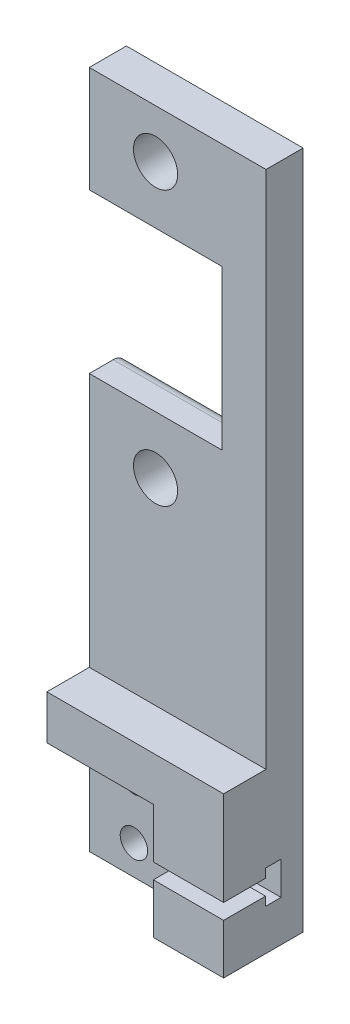
SolidWorks part; units mm, degrees
ref_plane "Front Plane" through (0, 0, 0) normal (0, 0, 1) x (1, 0, 0)
ref_plane "Top Plane" through (0, 0, 0) normal (0, 1, 0) x (1, 0, 0)
ref_plane "Right Plane" through (0, 0, 0) normal (1, 0, 0) x (0, 0, -1)
sketch "ProfileSketch3" plane through (0, 0, 0) normal (0, 0, 1) x (1, 0, 0)
  line L0 (0, 46.85) -> (15, 46.85)
  line L1 (0, 0) -> (20, 0)
  line L2 (0, 0) -> (0, 46.85)
  line L4 (20, 0) -> (20, 76.85)
  line L5 (15, 46.85) -> (15, 64.85)
  line L6 (15, 64.85) -> (0, 64.85)
  line L7 (0, 64.85) -> (0, 76.85)
  line L8 (0, 76.85) -> (20, 76.85)
  circle A0 centre (7.5, 40.35) radius 2.5
  circle A1 centre (7.5, 71.35) radius 2.5
  dimension "D8" = 5
  dimension "D6" = 20
  dimension "D1" = 46.85
  dimension "D2" = 15
  dimension "D4" = 12
  dimension "D5" = 5.5
  dimension "D7" = 6.5
  dimension "D3" = 31
  dimension "D9" = 7.5
  dimension "D10" = 18
  dimension "D11" = 6.5
extrude "ProfileBoss-Extrude1" add sketch "ProfileSketch3" along normal blind 9
sketch "MicroSwitchCutSketch4" plane through (0, 0, 9) normal (0, 0, 1) x (1, 0, 0)
  line L1 (0, 13.05) -> (12.05, 13.05)
  line L2 (0, 13.05) -> (0, 0)
  line L3 (0, 0) -> (12.05, 0)
  line L4 (12.05, 13.05) -> (12.05, 0)
  dimension "D1" = 12.05
  dimension "D2" = 13.05
extrude "MicroSwitchCut-Extrude1" cut sketch "MicroSwitchCutSketch4" against normal blind 4.8
sketch "Sketch5" plane through (0, 0, 4.2) normal (0, 0, 1) x (1, 0, 0)
  line L1 (0, 0) -> (12.05, 0) construction
  line L2 (12.05, 0) -> (12.05, 13.05) construction
  line L4 (12.05, 13.05) -> (0, 13.05) construction
  circle A0 centre (5.05, 9.7) radius 1.55
  circle A1 centre (5.05, 3.35) radius 1.55
  point P10 (11.05, 8.8)
  point P11 (0, 8.8)
  point P12 (15, 21.85)
  point P13 (11.05, 21.85)
  point P14 (15, 0)
  point P15 (15, 21.85)
  point P16 (0, 0)
  point P17 (15, 0)
  point P18 (0, 8.8)
  point P19 (0, 0)
  point P20 (-1, 8.8)
  point P21 (0, 8.8)
  point P22 (-1, 21.85)
  point P23 (-1, 8.8)
  point P24 (15, 21.85)
  point P25 (-1, 21.85)
  point P26 (15, 0)
  point P27 (15, 21.85)
  point P28 (0, 0)
  point P29 (15, 0)
  point P30 (0, 8.8)
  point P31 (0, 0)
  point P32 (11.05, 21.85)
  point P33 (-1, 21.85)
  point P34 (11.05, 8.8)
  point P35 (11.05, 21.85)
  point P36 (-1, 8.8)
  point P37 (0, 8.8)
  point P38 (0, 8.8)
  point P39 (11.05, 8.8)
  point P40 (-1, 21.85)
  point P41 (-1, 8.8)
  point P42 (11.05, 8.8)
  point P43 (11.05, 21.85)
  point P44 (0, 0)
  point P45 (15, 0)
  point P46 (0, 0)
  point P47 (0, 8.8)
  point P48 (-1, 21.85)
  point P49 (15, 21.85)
  point P50 (15, 0)
  point P51 (15, 21.85)
  point P52 (-1, 21.85)
  point P53 (-1, 8.8)
  point P54 (-1, 8.8)
  point P55 (0, 8.8)
  point P56 (-1, 21.85)
  point P57 (-1, 8.8)
  point P58 (-1, 21.85)
  point P59 (11.05, 21.85)
  point P60 (-1, 21.85)
  point P61 (-1, 8.8)
  point P62 (-1, 8.8)
  point P63 (11.05, 8.8)
  point P64 (11.05, 21.85)
  point P65 (11.05, 8.8)
  point P66 (2.75, 0)
  point P67 (-2.75, 0)
  point P68 (0, -2.75)
  point P69 (0, 2.75)
  dimension "D4" = 3.1
  dimension "D3" = 7
  dimension "D1" = 3.35
  dimension "D2" = 3.35
extrude "MicroSwitchMountingHolesCut-Extrude2" cut sketch "Sketch5" against normal blind 3.1
sketch "SmallChannelCableSketch6" plane through (0, 0, 9) normal (0, 0, 1) x (1, 0, 0)
  line L0 (12.05, 0) -> (12.05, 13.05) construction
  line L1 (12.05, 7.4) -> (20, 7.4)
  line L2 (12.05, 7.4) -> (12.05, 5.65)
  line L3 (12.05, 5.65) -> (20, 5.65)
  line L4 (20, 7.4) -> (20, 5.65)
  line L5 (20, 0) -> (20, 76.85) construction
  line L31 (12.05, 0) -> (20, 0) construction
  point P10 (1, 21.85)
  point P11 (1, 13.05)
  point P12 (16, 21.85)
  point P13 (1, 21.85)
  point P14 (16, 0)
  point P15 (16, 21.85)
  point P16 (12.05, 0)
  point P17 (16, 0)
  point P18 (1, 13.05)
  point P19 (0, 13.05)
  point P20 (1, 21.85)
  point P21 (1, 13.05)
  point P22 (16, 21.85)
  point P23 (1, 21.85)
  point P24 (16, 0)
  point P25 (16, 21.85)
  point P26 (0, 0)
  point P27 (16, 0)
  point P28 (0, 13.05)
  point P29 (0, 0)
  point P30 (12.05, 13.05)
  point P31 (1, 13.05)
  point P32 (1, 13.05)
  point P33 (0, 13.05)
  point P34 (12.05, 0)
  point P35 (12.05, 13.05)
  point P36 (0, 0)
  point P37 (12.05, 0)
  point P38 (0, 13.05)
  point P39 (0, 0)
  point P40 (12.05, 13.05)
  point P41 (1, 13.05)
  point P42 (12.05, 0)
  point P43 (12.05, 13.05)
  point P44 (5.05, 9.7)
  point P45 (6.5323, 10.1532)
  point P46 (5.05, 3.35)
  point P47 (6.5323, 3.8032)
  point P48 (5.05, 9.7)
  point P49 (6.5323, 10.1532)
  point P50 (5.05, 3.35)
  point P51 (6.5323, 3.8032)
  point P52 (0, 0)
  point P53 (16, 0)
  point P54 (0, 0)
  point P55 (0, 13.05)
  point P56 (1, 21.85)
  point P57 (16, 21.85)
  point P58 (16, 0)
  point P59 (16, 21.85)
  point P60 (1, 21.85)
  point P61 (1, 13.05)
  point P62 (1, 13.05)
  point P63 (0, 13.05)
  dimension "D1" = 1.75
  dimension "D2" = 5.65
extrude "SmallChannelCableCut-Extrude3" cut sketch "SmallChannelCableSketch6" against normal blind 4.75
sketch "LargeChannelCableSketch7" plane through (0, 0, 4.25) normal (0, 0, 1) x (1, 0, 0)
  line L0 (12.05, 7.4) -> (12.05, 13.05) construction
  line L1 (12.05, 8.4) -> (20, 8.4)
  line L2 (12.05, 8.4) -> (12.05, 4.65)
  line L3 (12.05, 4.65) -> (20, 4.65)
  line L4 (20, 8.4) -> (20, 4.65)
  line L5 (20, 0) -> (20, 5.65) construction
  line L6 (20, 7.4) -> (12.05, 7.4) construction
  dimension "D2" = 3.75
extrude "LargeChannelCableCut-Extrude4" cut sketch "LargeChannelCableSketch7" against normal blind 1.75
chamfer "Chamfer1" distance 1 angle 45 1 edges at (12.05, 6.525, 4.2)
sketch "Sketch7" plane through (0, 0, 0) normal (-1, 0, 0) x (0, 0, 1)
  line L0 (4.2, 13.05) -> (4.2, 0) construction
  line L1 (9, 76.85) -> (4.2, 76.85)
  line L2 (9, 76.85) -> (9, 18.05)
  line L3 (9, 18.05) -> (4.2, 18.05)
  line L4 (4.2, 76.85) -> (4.2, 18.05)
  line L5 (4.2, 13.05) -> (9, 13.05) construction
  line L6 (9, 76.85) -> (0, 76.85) construction
  dimension "D1" = 5
  dimension "D2" = 4.8
extrude "BoltSpaceCut-Extrude1" cut sketch "Sketch7" against normal through all
fillet "Fillet1" radius 1.5 2 edges at (7.5, 46.85, 0) (7.5, 64.85, 0)
equation "\"SK8RodShaftSupportHeight\"= 42mm"
equation "\"SK8RodShaftSupportLength\"= 15mm"
equation "\"SK8MountHoleDiameter\"= 5mm"
equation "\"SK8RiserWidth\"= 6.75mm'Measured to meet Nema17 Mount Hole Center axis"
equation "\"SK8MountHoleFromSide\"= \"SK8RodShaftSupportLength\" / 2"
equation "\"SK8MountHoleFromEitherEnd\"= 5.5mm"
equation "\"MicroSwitchCutOutLength\"= 13.05mm"
equation "\"MicroSwitchHeight\"= 6.55mm"
equation "\"MicroSwitchMountingHoleOffsetFromSide\"= 3.35mm"
equation "\"MicroSwitchTerminalHeight\"= 3.5mm"
equation "\"MicroSwitchExtraMountingHeight\"= 2mm"
equation "\"MicroSwitchDepth\"= 2.8mm"
equation "\"MicroSwitchMountingHoleOffsetFromBottom\"= 7mm"
equation "\"M2HeatInsertHoleDiameter\"= 3mm + .1mm'Add .1mm for printing"
equation "\"M2HeatInsertHoleDepth\"= 3.1mm'Spec"
equation "\"D1@ProfileBoss-Extrude1\" = \"SK8RiserWidth\""
equation "\"D1@MicroSwitchCutSketch4\"=\"MicroSwitchCutOutHeight\""
equation "\"D2@MicroSwitchCutSketch4\" = \"MicroSwitchCutOutLength\""
equation "\"D1@MicroSwitchCut-Extrude1\"=\"MicroSwitchDepth\" + 2mm"
equation "\"D3@Sketch5\"=\"MicroSwitchMountingHoleOffsetFromBottom\""
equation "\"D4@Sketch5\"=\"M2HeatInsertHoleDiameter\""
equation "\"D1@MicroSwitchMountingHolesCut-Extrude2\" = \"M2HeatInsertHoleDepth\""
equation "\"MicroSwitchCutOutHeight\"= \"MicroSwitchExtraMountingHeight\" + \"MicroSwitchTerminalHeight\" + \"MicroSwitchHeight\""
equation "\"EndStopCableWidth\"= 3.75mm"
equation "\"D1@SmallChannelCableSketch6\" = \"EndStopCableDepth\""
equation "\"EndStopCableDepth\"= 1.75mm"
equation "\"D1@SmallChannelCableCut-Extrude3\"=\"EndStopCableDepth\" + 3mm"
equation "\"D1@LargeChannelCableSketch7\" =  ( \"EndStopCableWidth\" - \"EndStopCableDepth\" )  / 2"
equation "\"D2@LargeChannelCableSketch7\" = \"EndStopCableWidth\""
equation "\"D1@LargeChannelCableCut-Extrude4\" = \"EndStopCableDepth\""
equation "\"D6@ProfileSketch3\"=\"SK8RodShaftSupportLength\"  + 5mm"
equation "\"D1@Sketch5\"=\"MicroSwitchMountingHoleOffsetFromSide\""
equation "\"D2@Sketch5\"=\"MicroSwitchMountingHoleOffsetFromSide\""
equation "\"D2@SmallChannelCableSketch6\"=(\"MicroSwitchCutOutLength\" - \"EndStopCableDepth\")/2"
equation "\"D1@Sketch6\"= \"SK8MountHoleFromEitherEnd\""
equation "\"D1@ProfileSketch3\"=\"MicroSwitchCutOutLength\" + \"SK8MountHoleFromEitherEnd\" * 1.6 +25mm"
equation "\"D2@ProfileSketch3\"=\"SK8RodShaftSupportLength\""
equation "\"D4@ProfileSketch3\"=12mm"
equation "\"D5@ProfileSketch3\"=\"SK8MountHoleFromEitherEnd\""
equation "\"D8@ProfileSketch3\"=\"SK8MountHoleDiameter\""
equation "\"D9@ProfileSketch3\"=\"SK8RodShaftSupportLength\"/2"
equation "\"Nema17StepperMountSlotDistance\"=31"
equation "\"D3@ProfileSketch3\"=\"Nema17StepperMountSlotDistance\""
